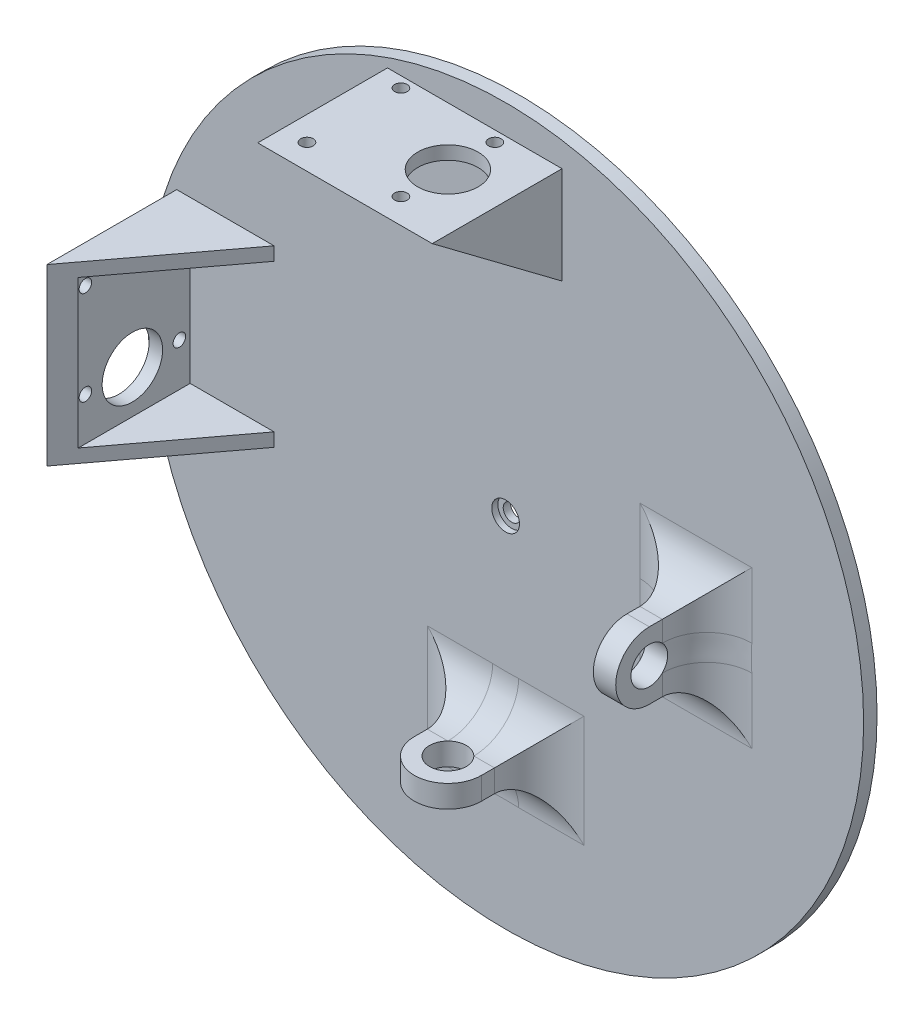
SolidWorks part; units mm, degrees
ref_plane "正面" through (0, 0, 0) normal (0, 0, 1) x (1, 0, 0)
ref_plane "平面" through (0, 0, 0) normal (0, 1, 0) x (1, 0, 0)
ref_plane "右側面" through (0, 0, 0) normal (1, 0, 0) x (0, 0, -1)
sketch "ｽｹｯﾁ5" plane through (0, 0, 0) normal (0, 1, 0) x (1, 0, 0)
  line L0 (-73.5, -32) -> (-73.5, 0)
  line L1 (-73.5, 0) -> (-49.5, 0)
  line L2 (-49.5, 0) -> (-73.5, -32)
  line L3 (-55, 0) -> (55, 0) construction
  dimension "D1" = 24
  dimension "D2" = 32
  dimension "D3" = 49.5
extrude "ﾎﾞｽ - 押し出し3" add sketch "ｽｹｯﾁ5" against normal blind 39 from offset 26.4
shell "ｼｪﾙ2" thickness 3 removed face at (-61.5, 6.9, 16)
sketch "ｽｹｯﾁ7" plane through (-70.5, 0, 0) normal (1, 0, 0) x (0, 0, -1)
  line L0 (-3, -9.6) -> (-3, 23.4) construction
  line L1 (-26.4, 0) -> (-5.4, 0) construction
  line L2 (-26.4, 0) -> (-26.4, 21) construction
  line L3 (-26.4, 21) -> (-5.4, 21) construction
  line L4 (-5.4, 0) -> (-5.4, 21) construction
  line L5 (-3, 23.4) -> (-28, 23.4) construction
  circle A0 centre (-15.9, 0) radius 6.75
  circle A1 centre (-26.4, 0) radius 1.4
  circle A2 centre (-5.4, 0) radius 1.4
  circle A3 centre (-5.4, 21) radius 1.4
  circle A4 centre (-26.4, 21) radius 1.4
  point P10 (-15.9, 0)
  dimension "D3" = 2.8
  dimension "D6" = 13.5
  dimension "D1" = 21
  dimension "D2" = 21
  dimension "D4" = 2.4
  dimension "D5" = 2.4
extrude "ｶｯﾄ - 押し出し5" cut sketch "ｽｹｯﾁ7" against normal through all
sketch "ｽｹｯﾁ1" plane through (0, 0, 0) normal (0, 0, 1) x (1, 0, 0)
  line L1 (56.5685, -56.5685) -> (-56.5685, -56.5685) construction
  line L2 (56.5685, -56.5685) -> (56.5685, 56.5685) construction
  line L3 (56.5685, 56.5685) -> (-56.5685, 56.5685) construction
  line L4 (-56.5685, -56.5685) -> (-56.5685, 56.5685) construction
  line L5 (56.5685, -56.5685) -> (-56.5685, 56.5685) construction
  line L6 (56.5685, 56.5685) -> (-56.5685, -56.5685) construction
  circle A0 centre (0, 0) radius 80
  point P0 (0, 0)
  dimension "D1" = 160
extrude "ﾎﾞｽ - 押し出し1" add sketch "ｽｹｯﾁ1" along normal blind 3 contours A0
sketch "ｽｹｯﾁ3" plane through (0, 0, 0) normal (0, 0, 1) x (1, 0, 0)
  circle A0 centre (0, 0) radius 1.9
  dimension "D1" = 3.8
extrude "ｶｯﾄ - 押し出し4" cut sketch "ｽｹｯﾁ3" against normal through all both and the other way through all
sketch "ｽｹｯﾁ8" plane through (0, 0, 3) normal (0, 0, 1) x (1, 0, 0)
  circle A0 centre (0, 0) radius 3.1
  dimension "D1" = 6.2
extrude "ｶｯﾄ - 押し出し6" cut sketch "ｽｹｯﾁ8" against normal blind 1.361 contours A0
ref_plane "平面1" through (0, -40, 0) normal (0, 1, 0) x (1, 0, 0)
sketch "ｽｹｯﾁ10" plane through (-147.416, -40, 0) normal (0, 1, 0) x (1, 0, 0)
  line L0 (139.916, 0) -> (154.916, 0)
  line L1 (154.916, 0) -> (154.916, -15.9)
  line L2 (139.916, 0) -> (139.916, -15.9)
  line L3 (59.416, 0) -> (235.416, 0) construction
  arc A2 (139.916, -15.9) -> (154.916, -15.9) centre (147.416, -15.9) ccw
  point P7 (147.416, 0)
  dimension "D1" = 15
  dimension "D2" = 15.9
extrude "ﾎﾞｽ - 押し出し5" add sketch "ｽｹｯﾁ10" against normal blind 5
sketch "ｽｹｯﾁ11" plane through (-147.416, -40, 0) normal (0, 1, 0) x (1, 0, 0)
  circle A0 centre (147.416, -15.9) radius 4.1
  arc A1 (139.916, -15.9) -> (154.916, -15.9) centre (147.416, -15.9) ccw construction
  dimension "D1" = 8.2
extrude "ｶｯﾄ - 押し出し8" cut sketch "ｽｹｯﾁ11" along normal up to surface (-5 mm away) up to face at (0, -45, 11.325)
fillet "ﾌｨﾚｯﾄ1" radius 10 4 edges at (7.5, -42.5, 3) (-7.5, -42.5, 3) (0, -45, 3) (0, -40, 3)
ref_plane "平面3" through (0, 0, 0) normal (0.7071, 0.7071, 0) x (-0.7071, 0.7071, 0)
mirror "ﾐﾗｰ1" about plane through (0, 0, 0) normal (0.7071, 0.7071, 0) of bodies 129
